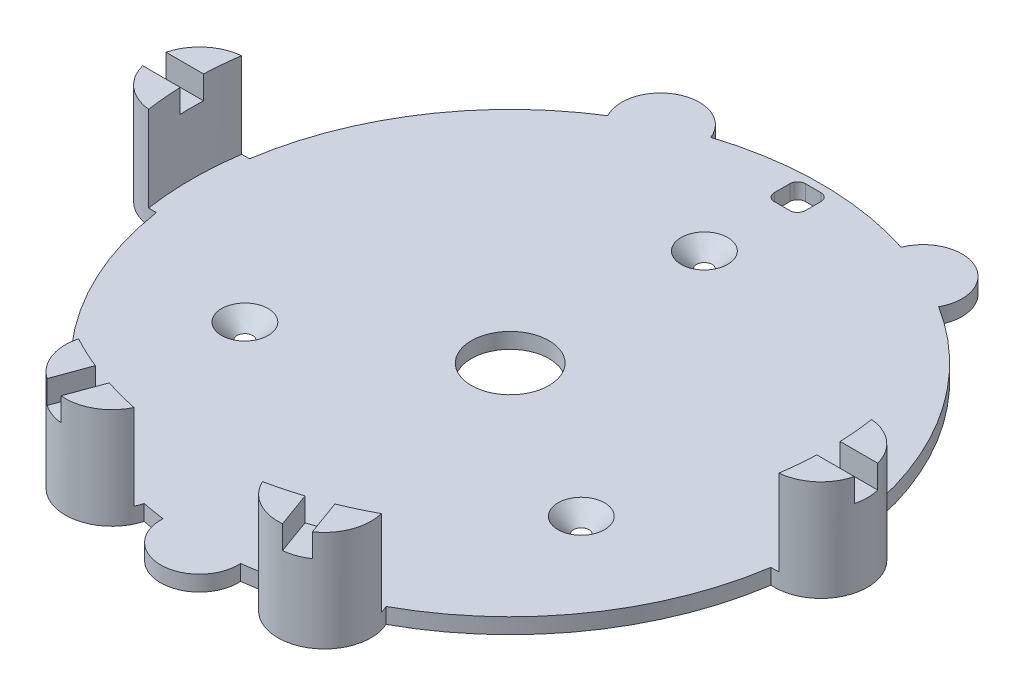
SolidWorks part; units mm, degrees
ref_plane "前视基准面" through (0, 0, 0) normal (0, 0, 1) x (1, 0, 0)
ref_plane "上视基准面" through (0, 0, 0) normal (0, 1, 0) x (1, 0, 0)
ref_plane "右视基准面" through (0, 0, 0) normal (1, 0, 0) x (0, 0, -1)
sketch "Sketch1" plane through (0, 0, 0) normal (0, 1, 0) x (1, 0, 0)
  line L0 (0, 0) -> (0, 25) construction
  circle A0 centre (0, 0) radius 40
  circle A1 centre (0, 0) radius 5
  circle A2 centre (0, 25) radius 1
  circle A3 centre (21.6506, -12.5) radius 1
  circle A4 centre (-21.6506, -12.5) radius 1
  point P12 (0, 0)
  dimension "D1" = 80
  dimension "D2" = 10
  dimension "D4" = 2
  dimension "D3" = 25
  dimension "D5" = 3
extrude "Boss-Extrude1" add sketch "Sketch1" along normal blind 2
sketch "Sketch2" plane through (0, 2, 0) normal (0, 1, 0) x (1, 0, 0)
  line L0 (0, 0) -> (0, 37) construction
  line L1 (0, 37) -> (0, 40) construction
  line L2 (-1, 35) -> (1, 35)
  line L3 (-2, 36) -> (-2, 38)
  line L4 (-1, 39) -> (1, 39)
  line L5 (2, 36) -> (2, 38)
  line L6 (-2, 35) -> (2, 39) construction
  line L7 (-2, 39) -> (2, 35) construction
  line L8 (0, 40) -> (0, 34) construction
  circle A0 centre (0, 0) radius 40 construction
  arc A1 (1, 35) -> (2, 36) centre (1, 36) ccw
  arc A2 (-1, 35) -> (-2, 36) centre (-1, 36) cw
  arc A3 (1, 39) -> (2, 38) centre (1, 38) cw
  arc A4 (-2, 38) -> (-1, 39) centre (-1, 38) cw
  dimension "D1" = 4
  dimension "D2" = 1
  dimension "D3" = 3
extrude "Cut-Extrude1" cut sketch "Sketch2" against normal up to next
sketch "Sketch6" plane through (0, 0, 0) normal (0, -1, 0) x (1, 0, 0)
  line L0 (0, 0) -> (40, 0) construction
  line L2 (0, 0) -> (0, 40) construction
  line L3 (0, 0) -> (13.6808, 37.5877) construction
  circle A0 centre (13.6808, 37.5877) radius 6
  circle A1 centre (0, 0) radius 40 construction
  circle A2 centre (40, 0) radius 6
  dimension "D1" = 20
  dimension "D3" = 12
  dimension "D2" = 90
extrude "Boss-Extrude4" add sketch "Sketch6" against normal blind 13
sketch "Sketch9" plane through (0, 13, 0) normal (0, 1, 0) x (1, 0, 0)
  circle A0 centre (0, 0) radius 41
  arc A1 (39.55, 5.9831) -> (7.9046, -39.2112) centre (0, 0) ccw construction
  dimension "D1" = 1
extrude "Cut-Extrude2" cut sketch "Sketch9" against normal up to surface (11 mm away) up to face at (11.4072, 2, 7.9874)
sketch "Sketch10" plane through (0, 13, 0) normal (0, 1, 0) x (1, 0, 0)
  line L0 (0, 0) -> (46, 0) construction
  line L1 (40.9726, 1.5) -> (45.8095, 1.5)
  line L2 (40.9726, -1.5) -> (45.8095, -1.5)
  line L3 (15.423, -37.9886) -> (17.0773, -42.5338)
  line L4 (12.6039, -39.0146) -> (14.2582, -43.5599)
  line L5 (40.9726, 1.5) -> (40.9726, -1.5) construction
  line L6 (0, 0) -> (40, 0) construction
  line L7 (0, 0) -> (13.6808, -37.5877) construction
  circle A0 centre (40, 0) radius 6 construction
  arc A1 (40.5625, -5.9736) -> (40.5625, 5.9736) centre (0, 0) ccw construction
  arc A2 (40.5625, -5.9736) -> (40.5625, 5.9736) centre (0, 0) ccw construction
  arc A3 (45.8095, 1.5) -> (45.8095, -1.5) centre (40, 0) cw
  arc A4 (40.9726, 1.5) -> (40.9726, -1.5) centre (0, 0) cw
  arc A5 (17.0773, -42.5338) -> (14.2582, -43.5599) centre (13.6808, -37.5877) cw
  arc A6 (15.423, -37.9886) -> (12.6039, -39.0146) centre (0, 0) cw
  point P25 (0, 0)
  dimension "D1" = 3
  dimension "D3" = 70
  dimension "D2" = 2
extrude "Cut-Extrude3" cut sketch "Sketch10" against normal blind 3
mirror "Mirror2" about plane through (0, 0, 0) normal (1, 0, 0) of "Cut-Extrude2", "Boss-Extrude4", "Cut-Extrude3"
chamfer "Chamfer1" distance 2 angle 45 3 edges at (-21.6506, 2, 13.5) (0, 2, -24) (21.6506, 2, 13.5)
sketch "Sketch11" plane through (0, 0, 0) normal (0, -1, 0) x (1, 0, 0)
  line L0 (0, 0) -> (0, 40) construction
  line L1 (0, 0) -> (0, 40) construction
  line L2 (0, 0) -> (16.9047, -36.2523) construction
  arc A0 (7.9046, 39.2112) -> (-7.9046, 39.2112) centre (0, 0) ccw construction
  circle A1 centre (0, 40) radius 5
  circle A2 centre (16.9047, -36.2523) radius 5
  circle A3 centre (-16.9047, -36.2523) radius 5
  dimension "D1" = 10
  dimension "D3" = 155
  dimension "D2" = 2
extrude "Boss-Extrude5" add sketch "Sketch11" against normal up to surface (2 mm away) up to face at (-21.6506, 2, 15.5)
